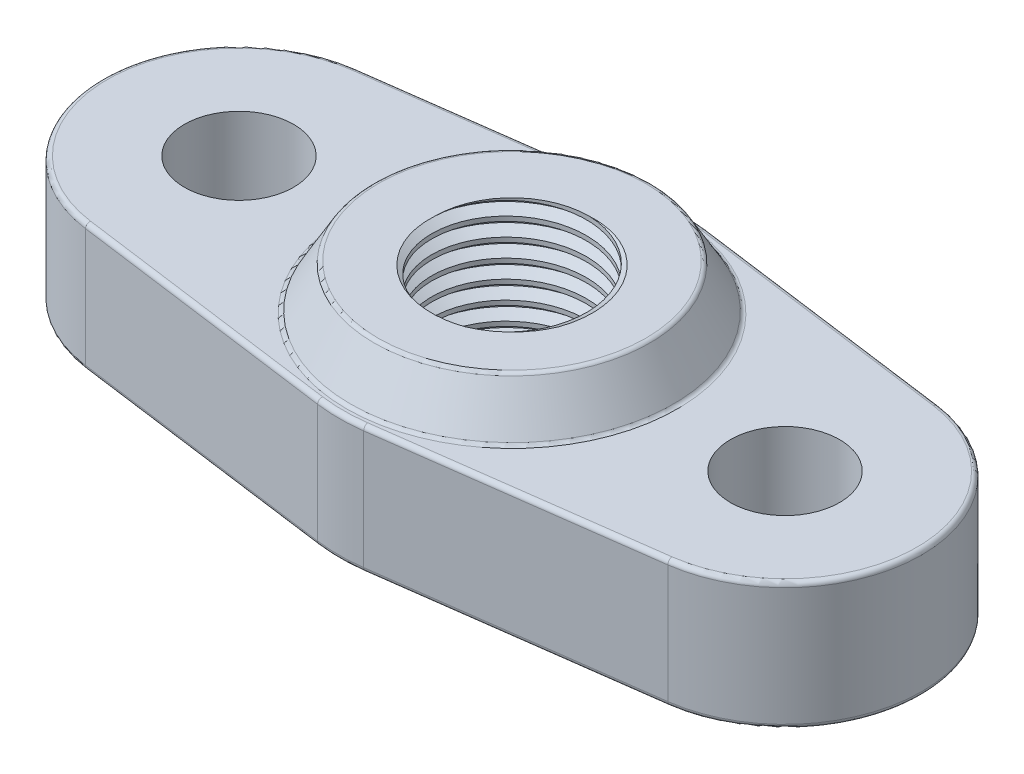
SolidWorks part; units mm, degrees
ref_plane "Front Plane" through (0, 0, 0) normal (0, 0, 1) x (1, 0, 0)
ref_plane "Top Plane" through (0, 0, 0) normal (0, 1, 0) x (1, 0, 0)
ref_plane "Right Plane" through (0, 0, 0) normal (1, 0, 0) x (0, 0, -1)
sketch "Sketch1" plane through (0, 0, 0) normal (0, 1, 0) x (1, 0, 0)
  line L0 (0, 0) -> (0, -53018.6562) construction
  line L1 (-2.1916, 0) -> (53016.4646, 0) construction
  line L2 (5.0667, 37.6607) -> (64, 29.7321)
  line L3 (5.0667, -37.6607) -> (64, -29.7321)
  line L4 (-5.0667, -37.6607) -> (-64, -29.7321)
  line L5 (-5.0667, 37.6607) -> (-64, 29.7321)
  arc A0 (-5.0667, -37.6607) -> (5.0667, -37.6607) centre (0, 0) ccw
  arc A1 (64, -29.7321) -> (64, 29.7321) centre (60, 0) ccw
  circle A2 centre (60, 0) radius 12
  circle A3 centre (-60, 0) radius 12
  arc A5 (-64, -29.7321) -> (-64, 29.7321) centre (-60, 0) cw
  arc A7 (5.0667, 37.6607) -> (-5.0667, 37.6607) centre (0, 0) ccw
  dimension "D1" = 60
  dimension "D2" = 24
  dimension "D4" = 76
  dimension "D3" = 120
extrude "Boss-Extrude1" add sketch "Sketch1" along normal blind 28
sketch "Sketch2" plane through (0, 0, 0) normal (0, 0, 1) x (1, 0, 0)
  line L0 (0, 0) -> (0, -50000) construction
  line L1 (0, 38) -> (30, 38)
  line L2 (30, 38) -> (35.7735, 28)
  line L3 (5.0667, 28) -> (64, 28) construction
  line L4 (35.7735, 28) -> (0, 28)
  line L5 (5.0667, 28) -> (-5.0667, 28) construction
  line L6 (0, 28) -> (0, 38)
  dimension "D1" = 60
  dimension "D2" = 60
  dimension "D3" = 10
revolve "Revolve1" add sketch "Sketch2" angle 360 about L0
hole_wizard "Ø1.0mm Dowel Hole1" positions "3DSketch1" profile "Sketch3" hole size "Ø1.0" standard "ANSI Metric" end condition up to next
sketch3d "3DSketch1"
  line L0 (0, 28, 0) -> (0, 38, 0) construction
  point P0 (0, 38, 0)
sketch "Sketch3" plane through (0, 38, 0) normal (1, 0, 0) x (0, 0, 1)
  line L0 (0, 0) -> (0, 38)
  line L1 (0, 38) -> (17, 38)
  line L2 (17, 38) -> (17, 0)
  line L5 (17, 0) -> (0, 0)
  line L11 (0, -6.35) -> (0, 107.95) construction
  dimension "Thru Hole Dia." = 34
  dimension "Thru Hole Depth" = 38
thread "Thread1" pitch 4 method cut profile "Thread Profile1" start angle 0, offset 4, length 0, pitch 4, diameter 34
ref_plane "Plane1" through (-17, 42, 0) normal (0, 0, 1) x (-1, 0, 0)
sketch "Thread Profile1" plane through (-17, 42, 0) normal (0, 0, 1) x (-1, 0, 0)
  line L0 (0, 0) -> (0, 4) construction
  line L1 (0, 0) -> (2.1651, 1.25)
  line L2 (2.1651, 1.25) -> (2.1651, 1.75)
  line L3 (2.1651, 1.75) -> (0, 3)
  line L4 (2.1651, 1.5) -> (0, 1.5) construction
  line L11 (0, 0) -> (0, 3)
  point P2 (0, 0)
  dimension "Pitch" = 4
  dimension "Profile_Angle" = 60
  dimension "Profile_Land" = 0.5
  dimension "Profile_Height" = 2.1651
fillet "Fillet1" radius 1 18 edges at (34.5333, 28, 33.6964) (0, 28, 38) (-34.5333, 28, 33.6964) (-90, 28, 0) (-34.5333, 28, -33.6964) (0, 28, -38) (34.5333, 28, -33.6964) (34.5333, 0, 33.6964) (0, 0, 38) (-34.5333, 0, 33.6964) (-90, 0, 0) (-34.5333, 0, -33.6964) (0, 0, -38) (34.5333, 0, -33.6964) (0, 28, 35.7735) (0, 38, 30) (90, 28, 0) (90, 0, 0)
